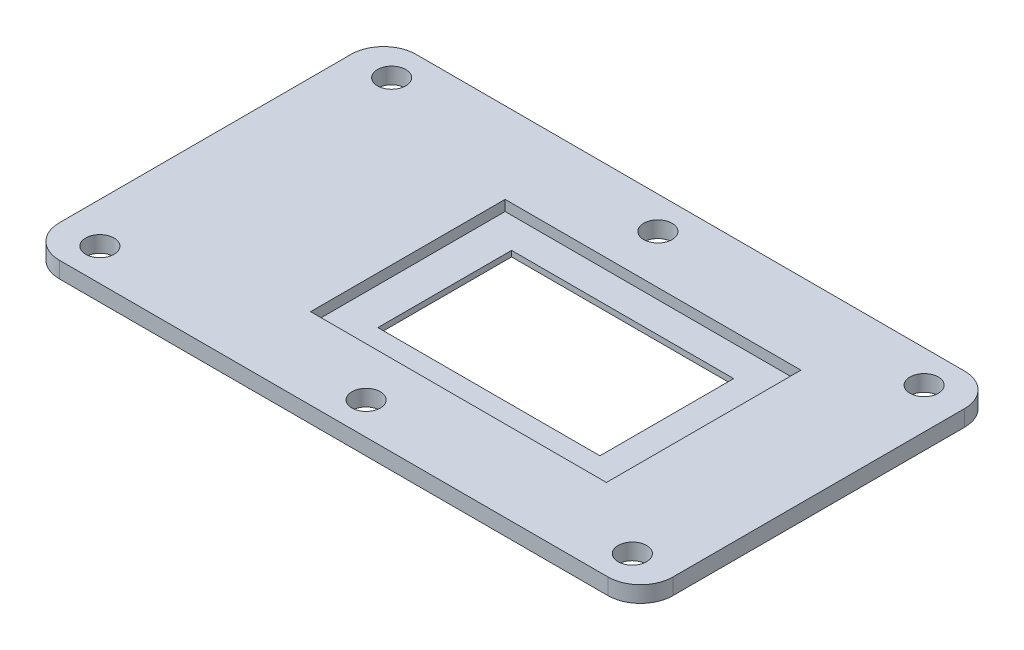
SolidWorks part; units mm, degrees
ref_plane "Front Plane" through (0, 0, 0) normal (0, 0, 1) x (1, 0, 0)
ref_plane "Top Plane" through (0, 0, 0) normal (0, 1, 0) x (1, 0, 0)
ref_plane "Right Plane" through (0, 0, 0) normal (1, 0, 0) x (0, 0, -1)
sketch "Sketch1" plane through (0, 0, 0) normal (0, 1, 0) x (1, 0, 0)
  line L1 (-13.7, -8.25) -> (13.7, -8.25)
  line L2 (-13.7, -8.25) -> (-13.7, 8.25)
  line L3 (-13.7, 8.25) -> (13.7, 8.25)
  line L4 (13.7, -8.25) -> (13.7, 8.25)
  line L5 (-13.7, -8.25) -> (13.7, 8.25) construction
  line L6 (-13.7, 8.25) -> (13.7, -8.25) construction
  line L7 (-18.25, 12) -> (18.25, 12)
  line L8 (-18.25, 12) -> (-18.25, -12)
  line L9 (-18.25, -12) -> (18.25, -12)
  line L10 (18.25, 12) -> (18.25, -12)
  line L11 (-18.25, 12) -> (18.25, -12) construction
  line L12 (-18.25, -12) -> (18.25, 12) construction
  line L13 (-33.25, 13) -> (22.45, 13)
  line L14 (-33.25, 13) -> (-33.25, -13)
  line L15 (-33.25, -13) -> (22.45, -13)
  line L16 (22.45, 13) -> (22.45, -13)
  line L20 (-5.4, 13) -> (-5.4, 28.3625) construction
  line L21 (-33.25, 0) -> (-43.25, 0) construction
  line L23 (-39.25, 22) -> (28.45, 22)
  line L24 (-43.25, 18) -> (-43.25, -18)
  line L25 (-39.25, -22) -> (28.45, -22)
  line L26 (32.45, 18) -> (32.45, -18)
  circle A0 centre (-5.4, 18) radius 1.75
  circle A1 centre (-38.25, 18) radius 1.75
  circle A2 centre (27.45, 18) radius 1.75
  circle A3 centre (27.45, -18) radius 1.75
  circle A4 centre (-5.4, -18) radius 1.75
  circle A5 centre (-38.25, -18) radius 1.75
  arc A6 (-43.25, -18) -> (-39.25, -22) centre (-39.25, -18) ccw
  arc A7 (28.45, -22) -> (32.45, -18) centre (28.45, -18) ccw
  arc A8 (28.45, 22) -> (32.45, 18) centre (28.45, 18) cw
  arc A9 (-39.25, 22) -> (-43.25, 18) centre (-39.25, 18) ccw
  point P0 (0, 0)
  point P5 (0, 0)
  point P15 (-33.25, 0)
  point P24 (-43.25, 0)
  dimension "D8" = 3.5
  dimension "D9" = 3.5
  dimension "D10" = 5
  dimension "D11" = 5
  dimension "D12" = 5
  dimension "D13" = 5
  dimension "D14" = 4
  dimension "D15" = 4
  dimension "D1" = 16.5
  dimension "D2" = 27.4
  dimension "D3" = 24
  dimension "D4" = 36.5
  dimension "D5" = 8.75
  dimension "D6" = 26
  dimension "D7" = 19.55
extrude "Boss-Extrude1" add sketch "Sketch1" along normal blind 2 contours L23 A9 L24 A6 L25 A7 L26 A8 A5 A2 A1 A0 L13 L16 L15 L14 A3 A4 | L16 L13 L14 L15 L7 L10 L9 L8 region at (-5.4, 0, -12.3853) region at (-5.4, 0, -21.1244)
extrude "Boss-Extrude2" add sketch "Sketch1<3>" along normal blind 0.7 contours L10 L7 L8 L9 L4 L1 L2 L3 region at (0, 0, -11.5632)
sketch "Sketch1<3>" plane through (0, 0, 0) normal (0, 1, 0) x (1, 0, 0) same geometry as "Sketch1"
